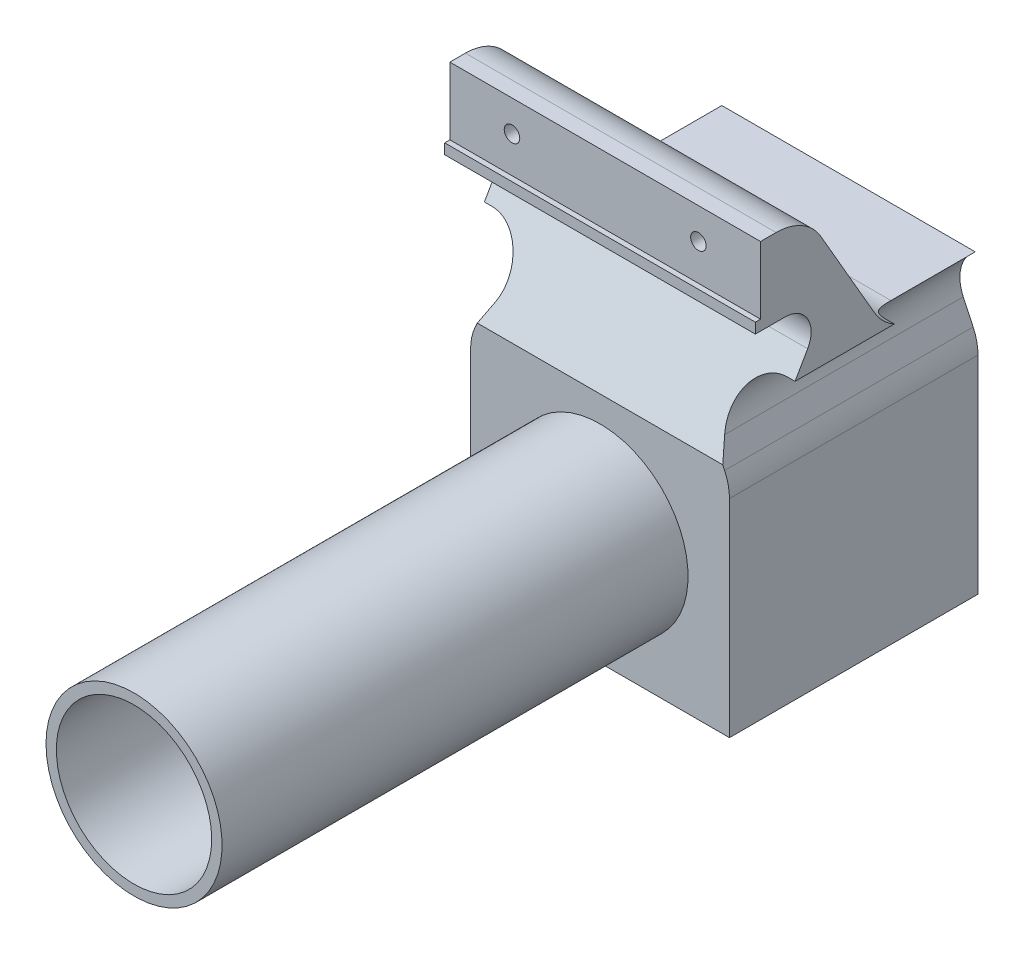
SolidWorks part; units mm, degrees
ref_plane "Front Plane" through (0, 0, 0) normal (0, 0, 1) x (1, 0, 0)
ref_plane "Top Plane" through (0, 0, 0) normal (0, 1, 0) x (1, 0, 0)
ref_plane "Right Plane" through (0, 0, 0) normal (1, 0, 0) x (0, 0, -1)
sketch "Sketch2" plane through (0, 0, 0) normal (0, 0, 1) x (1, 0, 0)
  line L0 (0, 0) -> (35439.1965, 0) construction
  line L1 (0, 0) -> (0, -35439.1965) construction
  line L2 (-25, 0) -> (-25, 40)
  line L3 (-24.0631, 44.2262) -> (-22.1558, 48.3163)
  line L4 (-28.5, 58.2746) -> (-30, 58.2746)
  line L5 (-30, 58.2746) -> (-30, 85)
  line L6 (-30, 85) -> (30, 85)
  line L7 (25, 0) -> (25, 40)
  line L8 (30, 58.2746) -> (30, 85)
  line L9 (28.5, 58.2746) -> (30, 58.2746)
  line L10 (24.0631, 44.2262) -> (22.1558, 48.3163)
  line L11 (-25, 0) -> (25, 0)
  arc A0 (-25, 40) -> (-24.0631, 44.2262) centre (-15, 40) cw
  arc A1 (-22.1558, 48.3163) -> (-28.5, 58.2746) centre (-28.5, 51.2746) ccw
  circle A2 centre (0, 23) radius 8
  circle A3 centre (-15, 23) radius 2.5
  circle A5 centre (0, 23) radius 15 construction
  circle A6 centre (15, 23) radius 2.5
  arc A7 (22.1558, 48.3163) -> (28.5, 58.2746) centre (28.5, 51.2746) cw
  arc A8 (25, 40) -> (24.0631, 44.2262) centre (15, 40) ccw
  point P30 (0, 85)
  dimension "D1" = 10
  dimension "D2" = 7
  dimension "D6" = 16
  dimension "D7" = 23
  dimension "D8" = 5
  dimension "D9" = 30
  dimension "D3" = 45
  dimension "D4" = 60
  dimension "D5" = 50
  dimension "D10" = 25
  dimension "D11" = 40
  dimension "D12" = 1.5
extrude "Boss-Extrude1" add sketch "Sketch2" against normal blind 48 contours L7 A8 L10 A7 L9 L8 L6 L5 L4 A1 L3 A0 L2 L11 A6 A3 A2 | A6 | A3 region at (0, 45.3405, 0) region at (-15, 23, 0) region at (15, 23, 0)
sketch "Sketch3" plane through (0, 0, 0) normal (1, 0, 0) x (0, 0, -1)
  line L0 (48, 57) -> (31.7128, 57)
  line L2 (48, 0) -> (0, 0) construction
  line L3 (23.0526, 62) -> (12.6603, 80)
  line L4 (0, 85) -> (4, 85)
  line L5 (48, 85) -> (0, 85) construction
  line L6 (0, 85) -> (0, 70)
  line L8 (0, 70) -> (5.7735, 70)
  line L9 (10.1036, 62.5) -> (0, 45)
  line L10 (0, 0) -> (0, 40) construction
  line L12 (1, 85) -> (1, 70)
  line L13 (4, 85) -> (48, 85)
  line L14 (48, 85) -> (48, 57)
  line L15 (0, 45) -> (0, 70)
  line L16 (48, 0) -> (48, 40) construction
  line L17 (0, 72) -> (1, 72)
  arc A0 (31.7128, 57) -> (23.0526, 62) centre (31.7128, 67) cw
  arc A1 (12.6603, 80) -> (4, 85) centre (4, 75) ccw
  arc A2 (5.7735, 70) -> (10.1036, 62.5) centre (5.7735, 65) cw
  dimension "D2" = 10
  dimension "D4" = 10
  dimension "D9" = 5
  dimension "D1" = 57
  dimension "D3" = 120
  dimension "D5" = 4
  dimension "D6" = 150
  dimension "D7" = 1
  dimension "D8" = 15
  dimension "D10" = 40
  dimension "D11" = 2
extrude "Cut-Extrude1" cut sketch "Sketch3" against normal through all both and the other way through all contours L12 L4 L6 L8 region at (0, 78.5, -0.5)
extrude "Cut-Extrude2" cut sketch "Sketch3<3>" against normal through all both and the other way through all contours A1 L3 A0 L0 L14 L13 | A2 L8 L15 L9 region at (0, 72.4163, -32.4563) region at (0, 60.9857, -4.1363)
sketch "Sketch3<3>" plane through (0, 0, 0) normal (1, 0, 0) x (0, 0, -1) same geometry as "Sketch3"
sketch "Sketch4" plane through (0, 0, -1) normal (0, 0, 1) x (1, 0, 0)
  line L0 (0, 23) -> (0, 111.5717) construction
  line L1 (-30, 85) -> (30, 85) construction
  circle A0 centre (-18, 79) radius 1.5
  circle A1 centre (18, 79) radius 1.5
  dimension "D1" = 36
  dimension "D2" = 6
  dimension "D3" = 3
extrude "Cut-Extrude3" cut sketch "Sketch4" against normal blind 5
extrude "Cut-Extrude4" cut sketch "Sketch2<4>" along normal blind 5 from surface contours A3 | A6 region at (-15, 23, 0) region at (15, 23, 0) starting at face at (8, 23, -48)
sketch "Sketch2<4>" plane through (0, 0, 0) normal (0, 0, 1) x (1, 0, 0) same geometry as "Sketch2"
sketch "Sketch6" plane through (0, 0, 0) normal (0, 0, 1) x (1, 0, 0)
  circle A0 centre (0, 23) radius 17
  circle A1 centre (0, 23) radius 15
  dimension "D1" = 34
  dimension "D2" = 30
extrude "Boss-Extrude2" add sketch "Sketch6" along normal blind 90
sketch "Sketch7" plane through (0, 0, 0) normal (0, 0, 1) x (1, 0, 0)
  circle A1 centre (0, 23) radius 15
  circle A2 centre (0, 23) radius 15
  dimension "D1" = 0
extrude "Cut-Extrude6" cut sketch "Sketch7" against normal offset from surface (38 mm away) 10 contours A2 up to face at (-12.5, 23, -48)
sketch "Sketch8" plane through (0, 0, 0) normal (0, -1, 0) x (1, 0, 0)
  line L0 (25, -48) -> (25, 0) construction
  line L1 (-25, -48) -> (25, -48) construction
  circle A0 centre (0, -24) radius 15
  point P4 (25, -24)
  point P7 (0, -48)
  dimension "D1" = 30
extrude "Cut-Extrude7" cut sketch "Sketch8" against normal up to next
